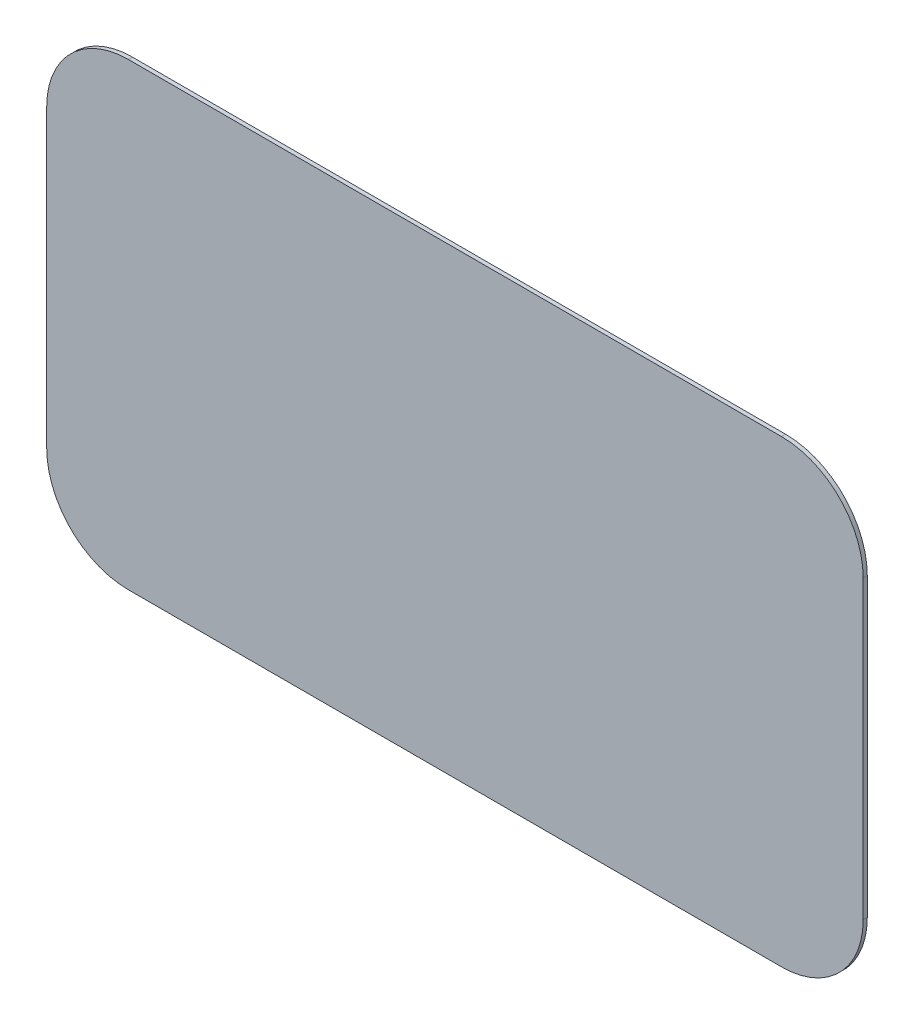
SolidWorks part; units mm, degrees
ref_plane "Спереди" through (0, 0, 0) normal (0, 0, 1) x (1, 0, 0)
ref_plane "Сверху" through (0, 0, 0) normal (0, 1, 0) x (1, 0, 0)
ref_plane "Справа" through (0, 0, 0) normal (1, 0, 0) x (0, 0, -1)
other "Configuration Table"
sketch "Эскиз1" plane through (0, 0, 0) normal (0, 0, 1) x (1, 0, 0)
  line L1 (-10, 5.625) -> (10, 5.625)
  line L2 (-10, 5.625) -> (-10, -5.625)
  line L3 (-10, -5.625) -> (10, -5.625)
  line L4 (10, 5.625) -> (10, -5.625)
  line L5 (0, -5.625) -> (0, 5.625) construction
  line L6 (-10, 0) -> (10, 0) construction
  point P0 (0, 0)
  dimension "D1" = 20
  dimension "D2" = 11.25
extrude "Бобышка-Вытянуть1" add sketch "Эскиз1" along normal blind 0.1
fillet "Скругление1" radius 2 4 edges at (-10, -5.625, 0.05) (-10, 5.625, 0.05) (10, -5.625, 0.05) (10, 5.625, 0.05)
equation "\"D2@Эскиз1\"=(\"D1@Эскиз1\"/16)*9"
